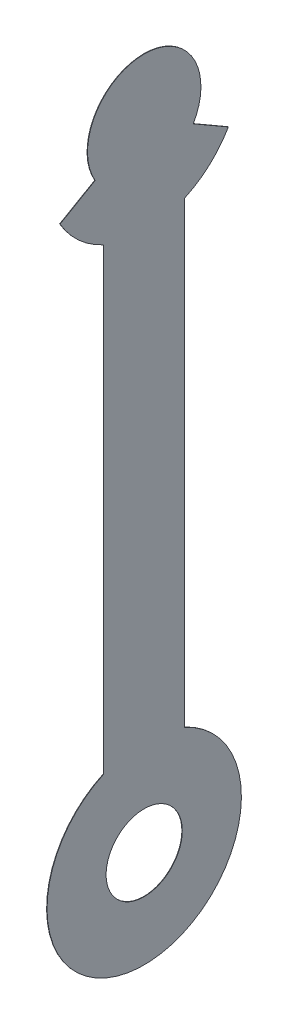
SolidWorks part; units mm, degrees
ref_plane "Front Plane" through (0, 0, 0) normal (0, 0, 1) x (1, 0, 0)
ref_plane "Top Plane" through (0, 0, 0) normal (0, 1, 0) x (1, 0, 0)
ref_plane "Right Plane" through (0, 0, 0) normal (1, 0, 0) x (0, 0, -1)
sketch "Sketch1" plane through (0, 0, 0) normal (1, 0, 0) x (0, 0, -1)
  line L0 (0, 0) -> (0, -392) construction
  line L1 (-30.3109, -17.5) -> (-51.9615, -30)
  line L2 (30.3109, -17.5) -> (51.9615, -30)
  line L3 (-20.3516, -196) -> (25.0726, -196) construction
  line L4 (-25, 0) -> (25, 0) construction
  line L5 (-25, -54.5436) -> (-25, -337.4564)
  line L6 (25, -54.5436) -> (25, -337.4564)
  arc A0 (-51.9615, -30) -> (51.9615, -30) centre (0, 0) ccw
  circle A1 centre (0, 0) radius 35
  circle A2 centre (0, -392) radius 60
  circle A3 centre (0, -392) radius 23.5
  point P15 (0, 0)
  dimension "D1" = 120
  dimension "D2" = 70
  dimension "D4" = 47
  dimension "D3" = 392
  dimension "D5" = 50
extrude "Boss-Extrude1" add sketch "Sketch1" against normal blind 0.25 contours A1 | A1 L1 A0 L2 | A2 L6 A0 L5 | A2 A3 region at (0, -40.189, 0) region at (0, 0, 0) region at (0, -196, 0) region at (0, -333.6971, 0)
